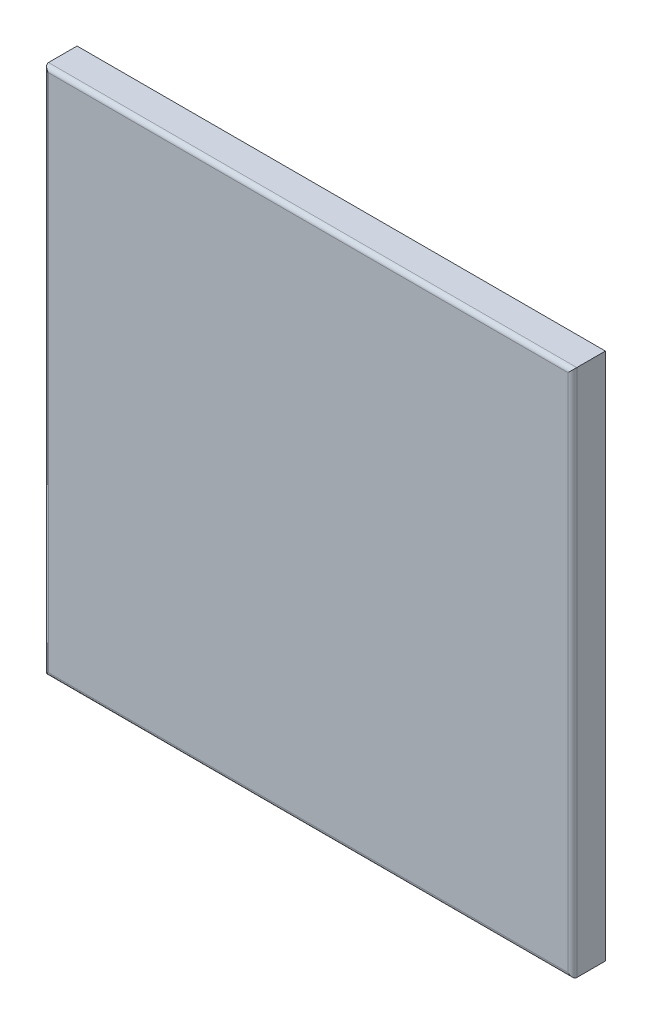
SolidWorks part; units mm, degrees
ref_plane "Front Plane" through (0, 0, 0) normal (0, 0, 1) x (1, 0, 0)
ref_plane "Top Plane" through (0, 0, 0) normal (0, 1, 0) x (1, 0, 0)
ref_plane "Right Plane" through (0, 0, 0) normal (1, 0, 0) x (0, 0, -1)
sketch "Sketch1" plane through (0, 0, 0) normal (0, 0, 1) x (1, 0, 0)
  line L1 (-152.4, -152.4) -> (152.4, -152.4)
  line L2 (-152.4, -152.4) -> (-152.4, 152.4)
  line L3 (-152.4, 152.4) -> (152.4, 152.4)
  line L4 (152.4, -152.4) -> (152.4, 152.4)
  line L5 (-152.4, -152.4) -> (152.4, 152.4) construction
  line L6 (-152.4, 152.4) -> (152.4, -152.4) construction
  point P0 (0, 0)
  dimension "D1" = 304.8
  dimension "D2" = 304.8
extrude "Boss-Extrude1" add sketch "Sketch1" along normal blind 2.54
sketch "Sketch2" plane through (0, 0, 2.54) normal (0, 0, 1) x (1, 0, 0)
  line L0 (149.86, 149.86) -> (-149.86, 149.86)
  line L1 (-149.86, 149.86) -> (-149.86, -149.86)
  line L2 (-149.86, -149.86) -> (149.86, -149.86)
  line L3 (149.86, -149.86) -> (149.86, 149.86)
  line L4 (152.4, -152.4) -> (152.4, 152.4)
  line L5 (152.4, 152.4) -> (-152.4, 152.4)
  line L6 (-152.4, 152.4) -> (-152.4, -152.4)
  line L7 (-152.4, -152.4) -> (152.4, -152.4)
  line L8 (152.4, -152.4) -> (152.4, 152.4)
  line L9 (152.4, 152.4) -> (-152.4, 152.4)
  line L10 (-152.4, 152.4) -> (-152.4, -152.4)
  line L11 (-152.4, -152.4) -> (152.4, -152.4)
  dimension "D1" = 0
  dimension "D2" = 2.54
extrude "Boss-Extrude2" add sketch "Sketch2" against normal blind 19.05
fillet "Fillet1" radius 2.54 5 edges at (0, -152.4, 2.54) (-152.4, 0, 2.54) (0, 152.4, 2.54) (152.4, 0, 2.54) (0, -149.86, -16.51)
